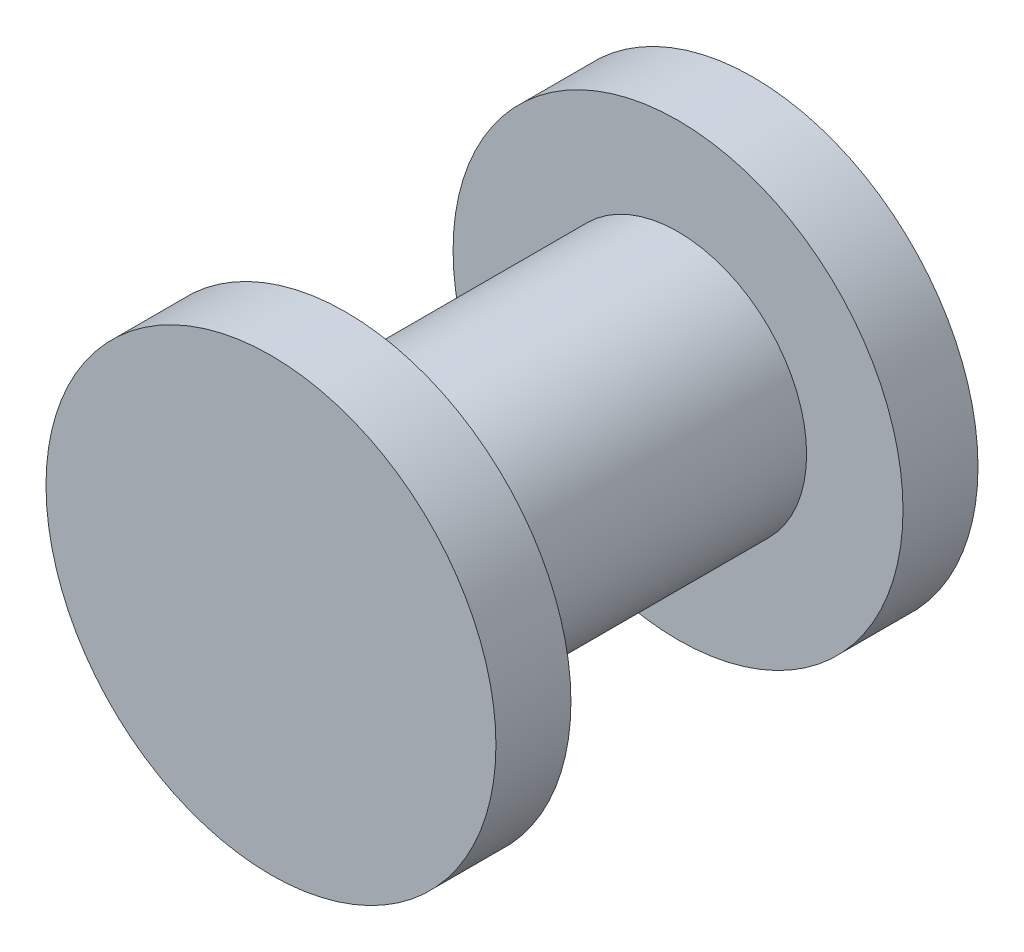
SolidWorks part; units mm, degrees
ref_plane "Front Plane" through (0, 0, 0) normal (0, 0, 1) x (1, 0, 0)
ref_plane "Top Plane" through (0, 0, 0) normal (0, 1, 0) x (1, 0, 0)
ref_plane "Right Plane" through (0, 0, 0) normal (1, 0, 0) x (0, 0, -1)
sketch "Sketch1" plane through (0, 0, 0) normal (0, 0, 1) x (1, 0, 0)
  circle A0 centre (0, 0) radius 21
extrude "Boss-Extrude1" add sketch "Sketch1" along normal blind 7
sketch "Sketch4" plane through (0, 0, 0) normal (0, 0, -1) x (-1, 0, 0)
  circle A0 centre (0, 0) radius 12
extrude "Boss-Extrude2" add sketch "Sketch4" along normal blind 31
sketch "Sketch5" plane through (0, 0, -31) normal (0, 0, -1) x (-1, 0, 0)
  circle A0 centre (0, 0) radius 21
extrude "Boss-Extrude3" add sketch "Sketch5" along normal blind 7
sketch "Sketch6" plane through (0, 0, 7) normal (0, 0, 1) x (1, 0, 0)
  line L0 (-2.503, 15.803) -> (-1.6476, 20.9353)
  line L2 (7.2638, 14.2561) -> (2.503, 15.803)
  line L4 (-2.503, 15.803) -> (-7.2638, 14.2561)
  line L6 (-11.3137, 11.3137) -> (-14.2561, 7.2638)
  line L8 (-15.803, 2.503) -> (-15.803, -2.503)
  line L10 (-14.2561, -7.2638) -> (-11.3137, -11.3137)
  line L12 (-7.2638, -14.2561) -> (-2.503, -15.803)
  line L14 (2.503, -15.803) -> (7.2638, -14.2561)
  line L16 (11.3137, -11.3137) -> (14.2561, -7.2638)
  line L18 (15.803, -2.503) -> (15.803, 2.503)
  line L20 (14.2561, 7.2638) -> (11.3137, 11.3137)
  line L61 (1.6476, 20.9353) -> (2.503, 15.803)
  line L62 (7.2638, 14.2561) -> (10.9725, 17.9054)
  line L63 (13.6384, 15.9685) -> (11.3137, 11.3137)
  line L64 (-7.2638, 14.2561) -> (-10.9725, 17.9054)
  line L65 (-13.6384, 15.9685) -> (-11.3137, 11.3137)
  line L66 (-14.2561, 7.2638) -> (-19.4015, 8.0364)
  line L67 (-20.4198, 4.9024) -> (-15.803, 2.503)
  line L68 (-15.803, -2.503) -> (-20.4198, -4.9024)
  line L69 (-19.4015, -8.0364) -> (-14.2561, -7.2638)
  line L70 (-11.3137, -11.3137) -> (-13.6384, -15.9685)
  line L71 (-7.2638, -14.2561) -> (-10.9725, -17.9054)
  line L72 (-2.503, -15.803) -> (-1.6476, -20.9353)
  line L73 (2.503, -15.803) -> (1.6476, -20.9353)
  line L74 (7.2638, -14.2561) -> (10.9725, -17.9054)
  line L75 (11.3137, -11.3137) -> (13.6384, -15.9685)
  line L76 (14.2561, -7.2638) -> (19.4015, -8.0364)
  line L77 (20.4198, -4.9024) -> (15.803, -2.503)
  line L78 (15.803, 2.503) -> (20.4198, 4.9024)
  line L79 (14.2561, 7.2638) -> (19.4015, 8.0364)
  line L80 (2.503, 15.803) -> (-2.503, 15.803)
  line L81 (-7.2638, 14.2561) -> (-11.3137, 11.3137)
  line L82 (-14.2561, 7.2638) -> (-15.803, 2.503)
  line L83 (-15.803, -2.503) -> (-14.2561, -7.2638)
  line L84 (-11.3137, -11.3137) -> (-7.2638, -14.2561)
  line L85 (-2.503, -15.803) -> (2.503, -15.803)
  line L86 (7.2638, -14.2561) -> (11.3137, -11.3137)
  line L87 (14.2561, -7.2638) -> (15.803, -2.503)
  line L88 (15.803, 2.503) -> (14.2561, 7.2638)
  line L89 (11.3137, 11.3137) -> (7.2638, 14.2561)
  arc A3 (-1.6476, 20.9353) -> (-10.9725, 17.9054) centre (0, 0) ccw
  arc A4 (1.6476, 20.9353) -> (10.9725, 17.9054) centre (0, 0) cw
  point P26 (0, 0)
